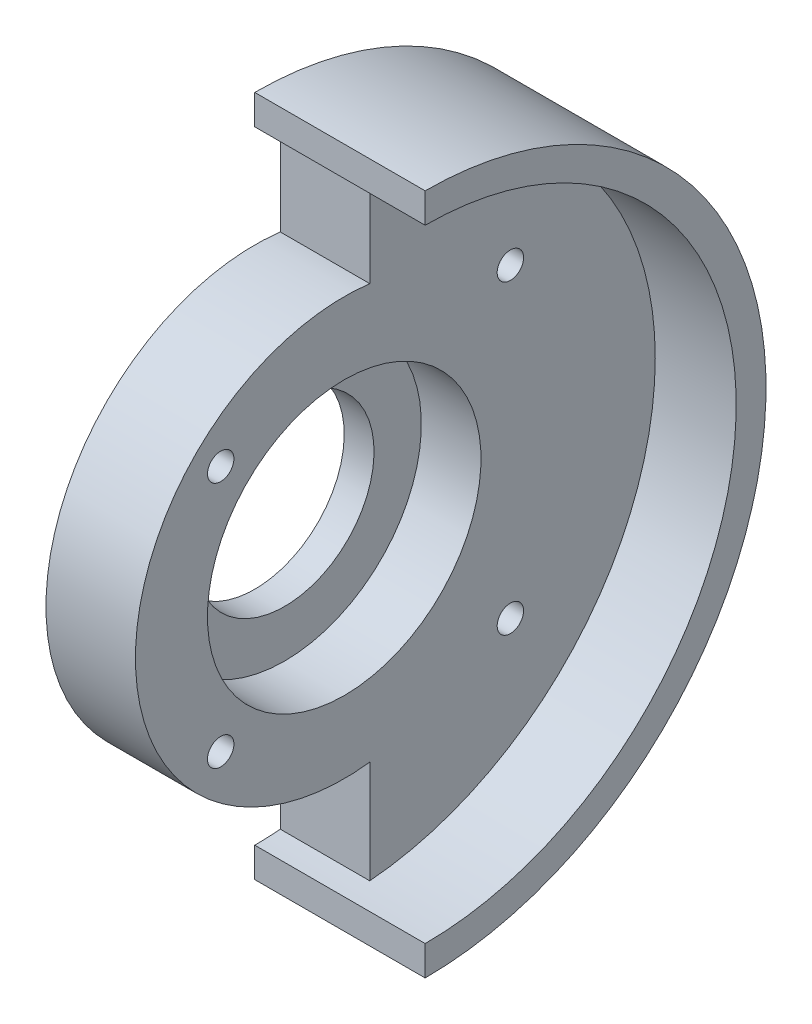
SolidWorks part; units mm, degrees
material "PLA 3D print"
ref_plane "Front Plane" through (0, 0, 0) normal (0, 0, 1) x (1, 0, 0)
ref_plane "Top Plane" through (0, 0, 0) normal (0, 1, 0) x (1, 0, 0)
ref_plane "Right Plane" through (0, 0, 0) normal (1, 0, 0) x (0, 0, -1)
sketch "Sketch1" plane through (0, 0, 0) normal (0, 0, 1) x (1, 0, 0)
  line L0 (20, 40) -> (20, 36.5)
  line L1 (20, 36.5) -> (10.5, 36.5)
  line L2 (10.5, 36.5) -> (10.5, 16.05)
  line L3 (10.5, 16.05) -> (3.5, 16.05)
  line L4 (3.5, 16.05) -> (3.5, 10.5)
  line L5 (3.5, 10.5) -> (0, 10.5)
  line L6 (0, 10.5) -> (0, 40)
  line L7 (0, 40) -> (20, 40)
  line L8 (20, 0) -> (0, 0) construction
  dimension "D1" = 20
  dimension "D2" = 7
  dimension "D3" = 9.5
  dimension "D4" = 10.5
  dimension "D5" = 16.05
  dimension "D6" = 36.5
  dimension "D7" = 40
revolve "Revolve1" add sketch "Sketch1" angle 360 about L8
sketch "Sketch2" plane through (10.5, 0, 0) normal (1, 0, 0) x (0, 0, -1)
  line L0 (3, 24.3156) -> (3, 36.3765)
  line L1 (3, -24.3156) -> (3, -36.3765)
  line L2 (0, 40) -> (0, 36.5)
  line L3 (0, -36.5) -> (0, -40)
  arc A0 (3, 36.3765) -> (0, 36.5) centre (0, 0) ccw
  arc A1 (3, 24.3156) -> (3, -24.3156) centre (0, 0) ccw
  circle A2 centre (-14.4957, 14.4957) radius 1.55
  circle A3 centre (0, 0) radius 36.5 construction
  arc A4 (3, 24.3156) -> (3, -24.3156) centre (0, 0) ccw construction
  circle A5 centre (19.5, -17.9444) radius 1.55
  circle A6 centre (19.5, 17.9444) radius 1.55
  circle A7 centre (19.5, 17.9444) radius 1.55 construction
  circle A9 centre (19.5, -17.9444) radius 1.55 construction
  arc A10 (0, 40) -> (0, -40) centre (0, 0) ccw
  circle A11 centre (0, 0) radius 40 construction
  arc A12 (0, -36.5) -> (3, -36.3765) centre (0, 0) ccw
  circle A13 centre (-14.4957, 14.4957) radius 1.55 construction
  circle A14 centre (-14.4957, -14.4957) radius 1.55
  circle A15 centre (-14.4957, -14.4957) radius 1.55 construction
extrude "Cut-Extrude1" cut sketch "Sketch2" against normal through all both and the other way through all
sketch "Sketch3" plane through (0, 0, 0) normal (-1, 0, 0) x (0, 0, 1)
  circle A0 centre (-19.5, 17.9444) radius 2.85
  circle A1 centre (14.4957, 14.4957) radius 2.85
  circle A2 centre (-19.5, -17.9444) radius 2.85
  circle A3 centre (14.4957, -14.4957) radius 2.85
  dimension "D1" = 5.7
extrude "Cut-Extrude2" cut sketch "Sketch3" against normal blind 5
